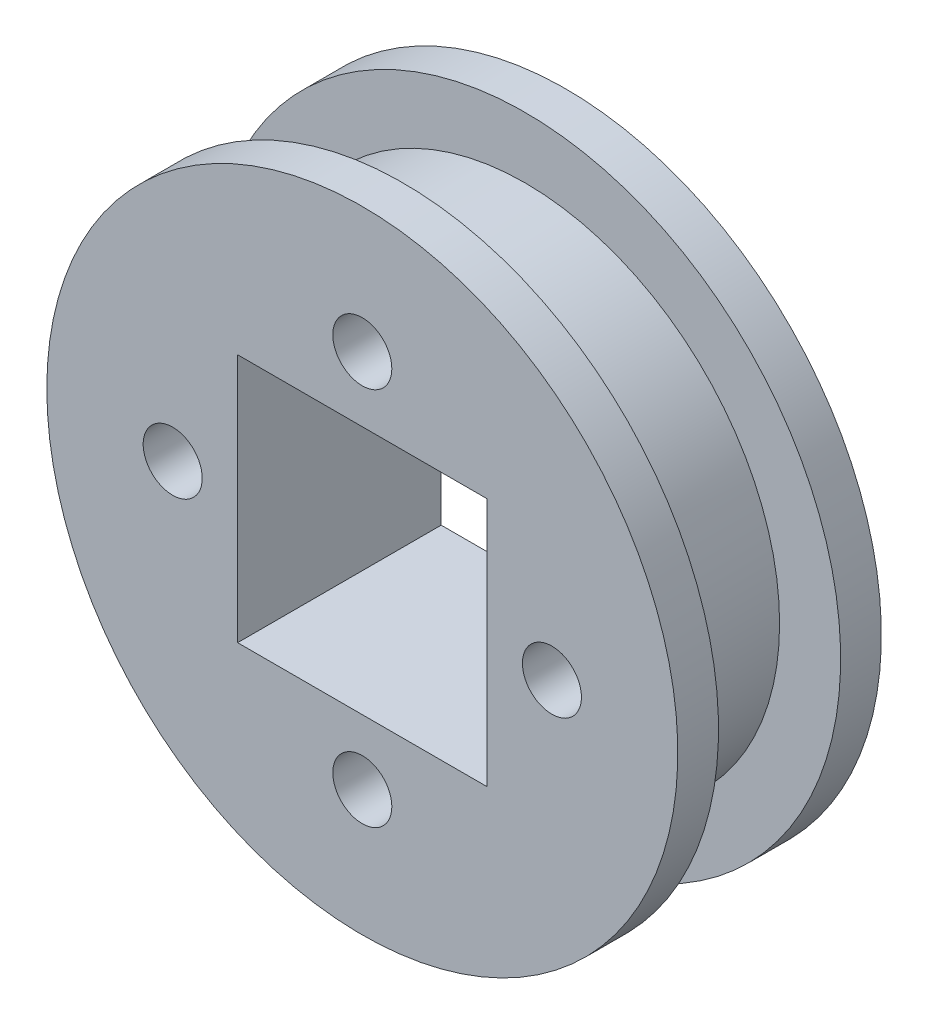
SolidWorks part; units mm, degrees
ref_plane "Front Plane" through (0, 0, 0) normal (0, 0, 1) x (1, 0, 0)
ref_plane "Top Plane" through (0, 0, 0) normal (0, 1, 0) x (1, 0, 0)
ref_plane "Right Plane" through (0, 0, 0) normal (1, 0, 0) x (0, 0, -1)
sketch "Sketch1" plane through (0, 0, 0) normal (0, 0, 1) x (1, 0, 0)
  circle A0 centre (0, 0) radius 12.5
  dimension "D2" = 25
extrude "Boss-Extrude1" add sketch "Sketch1" along normal mid plane 8
sketch "Sketch10" plane through (0, 0, 4) normal (0, 0, 1) x (1, 0, 0)
  circle A0 centre (0, 0) radius 12.5
  dimension "D1" = 25
sketch "Sketch13" plane through (0, 0, -4) normal (0, 0, -1) x (-1, 0, 0)
  circle A0 centre (0, 0) radius 15.5
  circle A1 centre (0, 0) radius 12.5 construction
  dimension "D1" = 3
extrude "Boss-Extrude2" add sketch "Sketch13" along normal blind 2
pattern_linear "LPattern1" count 2 spacing 8 along (0, 0, 1) of "Boss-Extrude2"
sketch "Sketch8" plane through (0, 0, 4) normal (0, 0, 1) x (1, 0, 0)
  line L2 (-6.125, 6.125) -> (6.125, 6.125)
  line L3 (-6.125, 6.125) -> (-6.125, -6.125)
  line L4 (-6.125, -6.125) -> (6.125, -6.125)
  line L5 (6.125, 6.125) -> (6.125, -6.125)
  line L6 (-6.125, 6.125) -> (6.125, -6.125) construction
  line L7 (-6.125, -6.125) -> (6.125, 6.125) construction
  point P5 (0, 0)
  point P14 (0, 0)
  dimension "D1" = 12.25
extrude "Cut-Extrude1" cut sketch "Sketch8" against normal up to next
sketch "Sketch11" plane through (0, 0, 4) normal (0, 0, 1) x (1, 0, 0)
  line L0 (6.125, -6.125) -> (6.125, 6.125) construction
  circle A0 centre (9.315, 0) radius 1.45
  circle A1 centre (0, -9.315) radius 1.45
  circle A2 centre (-9.315, 0) radius 1.45
  circle A3 centre (0, 9.315) radius 1.45
  point P13 (0, 0)
  dimension "D1" = 2.9
  dimension "D2" = 3.19
  dimension "D3" = 4
extrude "Cut-Extrude4" cut sketch "Sketch11" against normal up to next
equation "\"drumDiameter\"= 25"
equation "\"D2@Sketch1\"= \"drumDiameter\""
equation "\"drumLength\"=8"
equation "\"foamThickness\"= 5"
equation "\"drumAbove\"= 0.6"
equation "\"holderThicc\"= 2"
equation "\"D1@Boss-Extrude1\"=\"drumLength\""
equation "\"squareBarLength\"= 12.25"
equation "\"D1@Sketch8\"=\"squareBarLength\""
equation "\"D1@Sketch10\"=\"drumDiameter\""
equation "\"toothlen\"= 2.5"
